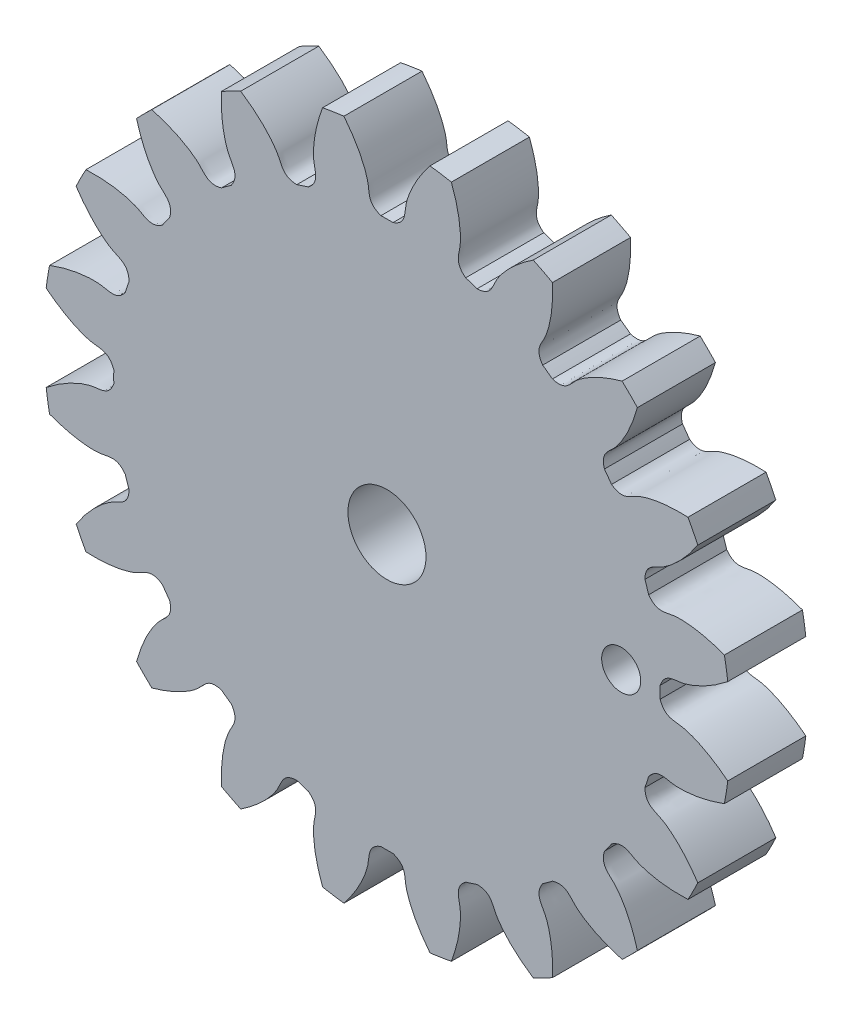
SolidWorks part; units mm, degrees
material "合金钢"
ref_plane "前视基准面" through (0, 0, 0) normal (0, 0, 1) x (1, 0, 0)
ref_plane "上视基准面" through (0, 0, 0) normal (0, 1, 0) x (1, 0, 0)
ref_plane "右视基准面" through (0, 0, 0) normal (1, 0, 0) x (0, 0, -1)
sketch "草图1" plane through (0, 0, 0) normal (0, 0, 1) x (1, 0, 0)
  circle A0 centre (0, 0) radius 44
extrude "凸台-拉伸1" add sketch "草图1" along normal blind 10
ref_axis "基准轴1" through (0, 0, -1.5) along (0, 0, 1)
sketch "草图2" plane through (0, 0, 0) normal (0, 0, 1) x (1, 0, 0)
  line L0 (0, 0) -> (0, 44) construction
  circle A0 centre (0, 0) radius 44 construction
  arc A1 (0.7733, 34.9915) -> (-0.7733, 34.9915) centre (0, 0) ccw
  arc A2 (12.7246, 49.993) -> (-12.7246, 49.993) centre (0, 0) ccw
  spline S0 degree 3 poles (0.7733, 34.9915) (2.4448, 35.5739) (2.2283, 36.7485) (2.4516, 37.88) (2.4756, 37.9902) (2.5052, 38.1145) (2.5412, 38.2528) (2.5839, 38.4048) (2.634, 38.5703) (2.6921, 38.749) (2.7587, 38.9408) (2.8343, 39.1453) (2.9194, 39.3622) (3.0147, 39.5913) (3.1205, 39.8322) (3.2375, 40.0846) (3.3661, 40.3481) (3.5067, 40.6223) (3.66, 40.9069) (3.8263, 41.2015) (4.0061, 41.5057) (4.1999, 41.819) (4.4081, 42.141) (4.6311, 42.4712) (4.8692, 42.8092) (5.1231, 43.1545) (5.3929, 43.5065) (5.679, 43.8649) (5.9819, 44.229) (6.3019, 44.5983) (6.6392, 44.9724) (6.9943, 45.3506) (7.3673, 45.7323) (7.7587, 46.1171) (8.1686, 46.5043) (8.5972, 46.8933) (9.0449, 47.2836) (9.5119, 47.6745) (9.9983, 48.0653) (10.5043, 48.4556) (11.0301, 48.8446) (11.7659, 49.3666) (12.3357, 49.7453) (12.7246, 49.993) knots 0 0 0 0 0.165916 0.170906 0.176664 0.183189 0.190482 0.198542 0.207371 0.216967 0.22733 0.238462 0.250361 0.263027 0.276462 0.290664 0.305634 0.321371 0.337876 0.355149 0.37319 0.391998 0.411574 0.431917 0.453028 0.474907 0.497554 0.520968 0.54515 0.570099 0.595817 0.622302 0.649554 0.677575 0.706363 0.735918 0.766242 0.797333 0.829191 0.861818 0.895212 0.929373 1 1 1 1
  spline S1 degree 3 poles (-0.7733, 34.9915) (-2.4448, 35.5739) (-2.2283, 36.7485) (-2.4516, 37.88) (-2.4756, 37.9902) (-2.5052, 38.1145) (-2.5412, 38.2528) (-2.5839, 38.4048) (-2.634, 38.5703) (-2.6921, 38.749) (-2.7587, 38.9408) (-2.8343, 39.1453) (-2.9194, 39.3622) (-3.0147, 39.5913) (-3.1205, 39.8322) (-3.2375, 40.0846) (-3.3661, 40.3481) (-3.5067, 40.6223) (-3.66, 40.9069) (-3.8263, 41.2015) (-4.0061, 41.5057) (-4.1999, 41.819) (-4.4081, 42.141) (-4.6311, 42.4712) (-4.8692, 42.8092) (-5.1231, 43.1545) (-5.3929, 43.5065) (-5.679, 43.8649) (-5.9819, 44.229) (-6.3019, 44.5983) (-6.6392, 44.9724) (-6.9943, 45.3506) (-7.3673, 45.7323) (-7.7587, 46.1171) (-8.1686, 46.5043) (-8.5972, 46.8933) (-9.0449, 47.2836) (-9.5119, 47.6745) (-9.9983, 48.0653) (-10.5043, 48.4556) (-11.0301, 48.8446) (-11.7659, 49.3666) (-12.3357, 49.7453) (-12.7246, 49.993) knots 0 0 0 0 0.165916 0.170906 0.176664 0.183189 0.190482 0.198542 0.207371 0.216967 0.22733 0.238462 0.250361 0.263027 0.276462 0.290664 0.305634 0.321371 0.337876 0.355149 0.37319 0.391998 0.411574 0.431917 0.453028 0.474907 0.497554 0.520968 0.54515 0.570099 0.595817 0.622302 0.649554 0.677575 0.706363 0.735918 0.766242 0.797333 0.829191 0.861818 0.895212 0.929373 1 1 1 1
extrude "切除-拉伸1" cut sketch "草图2" along normal through all
pattern_circular "阵列(圆周)1" count 20 every 18 about axis through (0, 0, -1.5) along (0, 0, 1) of "切除-拉伸1"
sketch "草图3" plane through (0, 0, 0) normal (0, 0, 1) x (1, 0, 0)
  circle A0 centre (0, 0) radius 40 construction
  dimension "Dn" = 80
sketch "草图4" plane through (0, 0, 10) normal (0, 0, 1) x (1, 0, 0)
  circle A0 centre (0, 0) radius 5
  dimension "D1" = 10
extrude "切除-拉伸2" cut sketch "草图4" against normal blind 10
sketch "草图5" plane through (0, 0, 10) normal (0, 0, 1) x (1, 0, 0)
  line L0 (0, 0) -> (30, 0) construction
  circle A0 centre (30, 0) radius 2.5
  dimension "D2" = 5
  dimension "D1" = 30
extrude "切除-拉伸3" cut sketch "草图5" against normal blind 10
